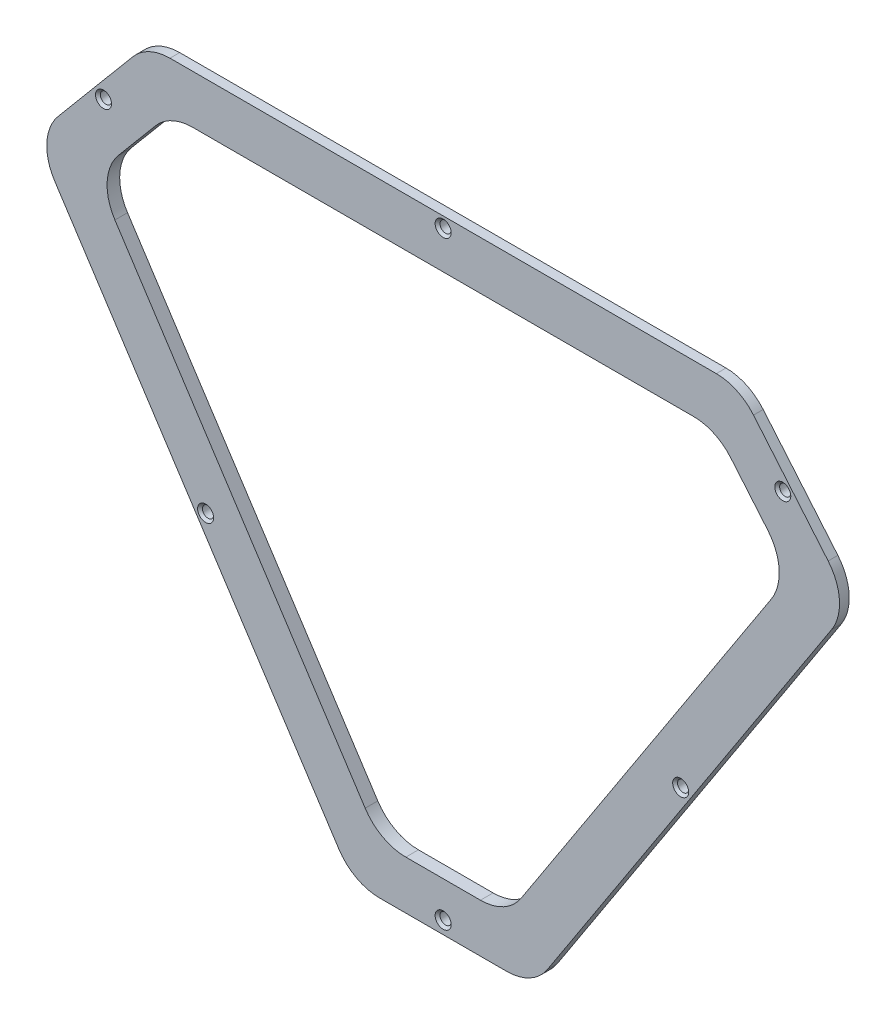
SolidWorks part; units mm, degrees
ref_plane "Plan de face" through (0, 0, 0) normal (0, 0, 1) x (1, 0, 0)
ref_plane "Plan de dessus" through (0, 0, 0) normal (0, 1, 0) x (1, 0, 0)
ref_plane "Plan de droite" through (0, 0, 0) normal (1, 0, 0) x (0, 0, -1)
sketch "Esquisse1" plane through (0, 0, 0) normal (0, 0, 1) x (1, 0, 0)
  line L0 (-40.8796, 34.6157) -> (81.0428, 34.6157)
  line L1 (81.0428, 34.6157) -> (104.1935, 7.0258)
  line L2 (104.1935, 7.0258) -> (38.618, -93.6745)
  line L3 (38.618, -93.6745) -> (1.5452, -93.6745)
  line L4 (1.5452, -93.6745) -> (-64.0303, 7.0258)
  line L5 (-64.0303, 7.0258) -> (-40.8796, 34.6157)
  line L6 (101.9984, 11.6642) -> (84.0469, 33.058) construction
  line L7 (-38.6879, 29.9157) -> (-58.1914, 6.6723) construction
  line L8 (-58.1914, 6.6723) -> (3.5509, -88.1416) construction
  line L10 (-44.0168, 31.3436) -> (-59.6403, 12.7242) construction
  line L12 (-60.3598, 0.8394) -> (-1.5758, -89.4315) construction
  line L13 (76.5196, 34.9157) -> (-36.3564, 34.9157) construction
  line L14 (99.8036, 12.7242) -> (84.1801, 31.3436) construction
  line L15 (41.7391, -89.4315) -> (100.523, 0.8394) construction
  line L16 (6.804, -93.9745) -> (33.3592, -93.9745) construction
  dimension "D1" = 0.3
  dimension "D2" = 0.3
  dimension "D3" = 0.3
  dimension "D4" = 0.3
  dimension "D5" = 0.3
  dimension "D6" = 0.3
extrude "Boss.-Extru.1" add sketch "Esquisse1" along normal blind 2
fillet "Congé1" radius 10 6 edges at (-40.8796, 34.6157, 1) (-64.0303, 7.0258, 1) (1.5452, -93.6745, 1) (38.618, -93.6745, 1) (104.1935, 7.0258, 1) (81.0428, 34.6157, 1)
sketch "Esquisse2" plane through (0, 0, 2) normal (0, 0, 1) x (1, 0, 0)
  line L0 (-36.2165, 24.6157) -> (-51.6072, 6.2738)
  line L1 (-51.6072, 6.2738) -> (6.9667, -83.6745)
  line L2 (6.9667, -83.6745) -> (33.1965, -83.6745)
  line L3 (-36.2165, 24.6157) -> (76.3797, 24.6157)
  line L4 (20.0816, 24.6157) -> (20.0816, -83.6745) construction
  line L5 (-59.9871, 0.8169) -> (-1.4132, -89.1315) construction
  line L6 (-43.8769, 31.0436) -> (-59.2676, 12.7017) construction
  line L7 (76.3797, 34.6157) -> (-36.2165, 34.6157) construction
  line L8 (6.9667, -93.6745) -> (33.1965, -93.6745) construction
  line L9 (91.7704, 6.2738) -> (33.1965, -83.6745)
  line L10 (76.3797, 24.6157) -> (91.7704, 6.2738)
  line L13 (41.5764, -89.1315) -> (100.1503, 0.8169) construction
  dimension "D1" = 10
  dimension "D2" = 10
  dimension "D3" = 10
  dimension "D4" = 10
extrude "Enlèv. mat.-Extru.1" cut sketch "Esquisse2" against normal blind 2
sketch "Esquisse4" plane through (0, 0, 0) normal (0, 0, -1) x (-1, 0, 0)
  line L0 (-78.245, 28.6157) -> (-96.7397, 6.5746)
  line L1 (-96.7397, 6.5746) -> (-35.3651, -87.6745)
  line L2 (-35.3651, -87.6745) -> (-4.7981, -87.6745)
  line L3 (-4.7981, -87.6745) -> (56.5764, 6.5746)
  line L4 (56.5764, 6.5746) -> (38.0817, 28.6157)
  line L5 (38.0817, 28.6157) -> (-78.245, 28.6157)
  line L6 (-76.3797, 34.6157) -> (36.2165, 34.6157) construction
  line L7 (-99.4309, 12.7017) -> (-84.0402, 31.0436) construction
  line L8 (43.8769, 31.0436) -> (59.2676, 12.7017) construction
  line L9 (59.9871, 0.8169) -> (1.4132, -89.1315) construction
  line L10 (-41.5764, -89.1315) -> (-100.1503, 0.8169) construction
  line L11 (-66.0524, -40.55) -> (-71.0803, -43.8241) construction
  line L12 (-20.0816, -87.6745) -> (-20.0816, -93.6745) construction
  line L13 (-6.9667, -93.6745) -> (-33.1965, -93.6745) construction
  line L14 (-20.0816, 28.6157) -> (-20.0816, 34.6157) construction
  line L15 (-87.4923, 17.5952) -> (-92.0886, 21.4519) construction
  line L16 (47.3291, 17.5952) -> (51.9253, 21.4519) construction
  line L17 (-76.3797, 24.6157) -> (-91.7704, 6.2738)
  line L18 (-91.7704, 6.2738) -> (-33.1965, -83.6745)
  line L19 (-33.1965, -83.6745) -> (-6.9667, -83.6745)
  line L20 (-6.9667, -83.6745) -> (51.6072, 6.2738)
  line L21 (51.6072, 6.2738) -> (36.2165, 24.6157)
  line L22 (-76.3797, 24.6157) -> (36.2165, 24.6157) construction
  line L23 (36.2165, 24.6157) -> (51.6072, 6.2738) construction
  line L24 (36.2165, 24.6157) -> (-76.3797, 24.6157)
  dimension "D1" = 6
extrude "Boss.-Extru.2" add sketch "Esquisse4" along normal blind 0.6
fillet "Congé2" radius 10 6 edges at (76.3797, 24.6157, 0.7) (91.7704, 6.2738, 0.7) (33.1965, -83.6745, 0.7) (6.9667, -83.6745, 0.7) (-36.2165, 24.6157, 0.7) (-51.6072, 6.2738, 0.7)
sketch "Esquisse3" plane through (0, 0, 2) normal (0, 0, 1) x (1, 0, 0)
  circle A1 centre (20.0816, -91.0581) radius 1.15
  circle A2 centre (-28.8728, -42.9318) radius 1.15
  circle A3 centre (20.0816, 32.4157) radius 1.15
  circle A4 centre (90.0767, 20.4269) radius 1.15
  circle A5 centre (69.0361, -42.9318) radius 1.15
  circle A6 centre (-49.9135, 20.4269) radius 1.15
  dimension "D1" = 2.3
extrude "Enlèv. mat.-Extru.2" cut sketch "Esquisse3" against normal blind 10
chamfer "Chanfrein1" distance 0.5 angle 45 6 edges at (91.2267, 20.4269, 2) (21.2316, 32.4157, 2) (-48.7635, 20.4269, 2) (70.1861, -42.9318, 2) (21.2316, -91.0581, 2) (-27.7228, -42.9318, 2)
chamfer "Chanfrein3" distance 0.6 angle 45 6 edges at (87.4923, 17.5952, -0.6) (20.0816, 28.6157, -0.6) (-47.3291, 17.5952, -0.6) (-25.8892, -40.55, -0.6) (20.0816, -87.6745, -0.6) (66.0524, -40.55, -0.6)
